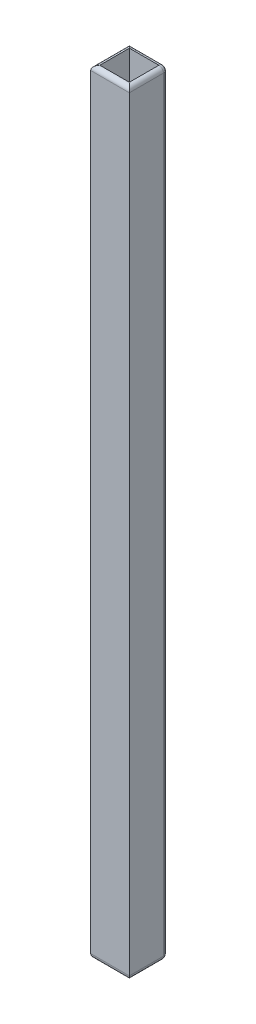
SolidWorks part; units mm, degrees
ref_plane "Front Plane" through (0, 0, 0) normal (0, 0, 1) x (1, 0, 0)
ref_plane "Top Plane" through (0, 0, 0) normal (0, 1, 0) x (1, 0, 0)
ref_plane "Right Plane" through (0, 0, 0) normal (1, 0, 0) x (0, 0, -1)
sketch "Sketch1" plane through (0, 0, 0) normal (0, 1, 0) x (1, 0, 0)
  line L1 (-4.25, -4.25) -> (4.25, -4.25)
  line L2 (-4.25, -4.25) -> (-4.25, 4.25)
  line L3 (-4.25, 4.25) -> (4.25, 4.25)
  line L4 (4.25, -4.25) -> (4.25, 4.25)
  line L5 (-4.25, -4.25) -> (4.25, 4.25) construction
  line L6 (-4.25, 4.25) -> (4.25, -4.25) construction
  line L7 (-3.25, -3.25) -> (3.25, -3.25)
  line L8 (-3.25, -3.25) -> (-3.25, 3.25)
  line L9 (-3.25, 3.25) -> (3.25, 3.25)
  line L10 (3.25, -3.25) -> (3.25, 3.25)
  line L11 (-3.25, -3.25) -> (3.25, 3.25) construction
  line L12 (-3.25, 3.25) -> (3.25, -3.25) construction
  point P0 (0, 0)
  point P6 (0, 0)
  dimension "D1" = 8.5
  dimension "D2" = 6.5
extrude "Boss-Extrude1" add sketch "Sketch1" along normal mid plane 170.2
fillet "Fillet1" radius 1 1 edges at (4.25, 0, -4.25)
fillet "Fillet2" radius 1 5 edges at (-4.25, 85.1, 0) (0, 85.1, 4.25) (4.25, 85.1, 0.5) (-0.5, 85.1, -4.25) (3.9571, 85.1, -3.9571)
fillet "Fillet3" radius 1 5 edges at (-4.25, -85.1, 0) (0, -85.1, 4.25) (4.25, -85.1, 0.5) (3.9571, -85.1, -3.9571) (-0.5, -85.1, -4.25)
